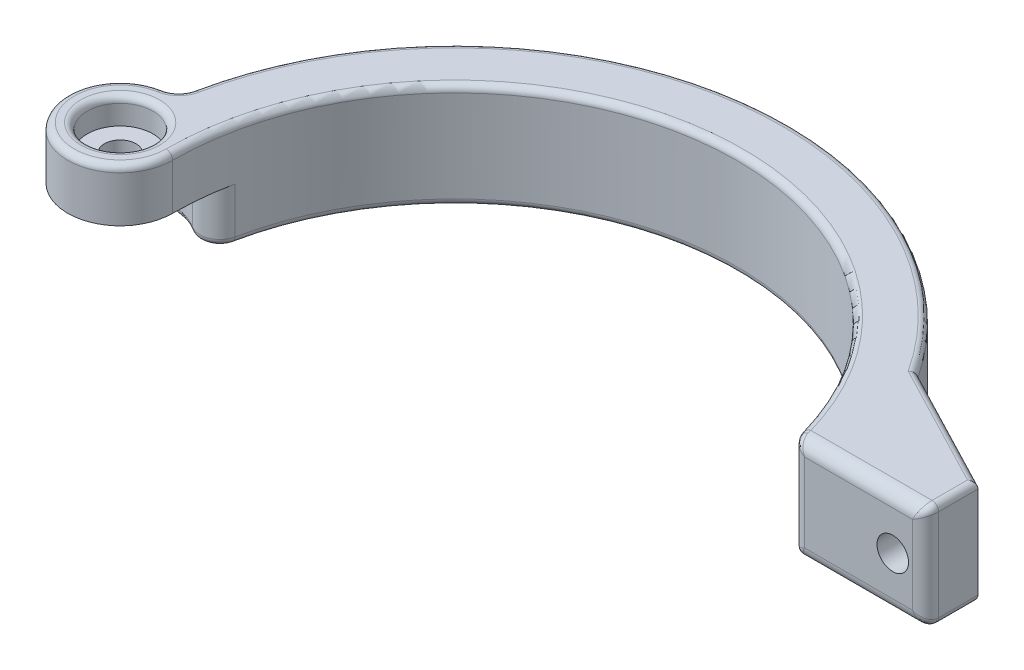
SolidWorks part; units mm, degrees
material "PET"
ref_plane "Front Plane" through (0, 0, 0) normal (0, 0, 1) x (1, 0, 0)
ref_plane "Top Plane" through (0, 0, 0) normal (0, 1, 0) x (1, 0, 0)
ref_plane "Right Plane" through (0, 0, 0) normal (1, 0, 0) x (0, 0, -1)
sketch "Sketch1" plane through (0, 0, 0) normal (0, 0, 1) x (1, 0, 0)
  line L0 (0, 0) -> (0, 16) construction
  line L1 (43, 0) -> (43, 16)
  line L2 (43, 16) -> (51, 16)
  line L3 (51, 16) -> (51, 0)
  line L4 (51, 0) -> (43, 0)
  dimension "D1" = 86
  dimension "D2" = 16
  dimension "D3" = 8
revolve "body" add sketch "Sketch1" angle 180 about L0
sketch "Sketch2" plane through (0, 16, 0) normal (0, 1, 0) x (1, 0, 0)
  circle A0 centre (-51, 0) radius 8
extrude "bearing_body" add sketch "Sketch2" against normal blind 8
sketch "Sketch3" plane through (0, 8, 0) normal (0, -1, 0) x (1, 0, 0)
  circle A0 centre (-51, 0) radius 8
  arc A1 (-43, 0) -> (-50.3725, -7.9754) centre (-51, 0) ccw construction
extrude "bearing_cutout" cut sketch "Sketch3" along normal through all
fillet "bearing_fillets" radius 3 2 edges at (-50.3725, 12, -7.9754) (-43, 4, 0)
sketch "Sketch4" plane through (0, 0, 0) normal (0, -1, 0) x (1, 0, 0)
  line L1 (51, 0) -> (41.821, 0)
  line L2 (51, 0) -> (51, -10)
  line L3 (51, -10) -> (41.821, -10)
  line L4 (41.821, 0) -> (41.821, -10)
  arc A0 (-50.3725, -7.9754) -> (51, 0) centre (0, 0) ccw construction
  arc A1 (-42.1202, -8.6538) -> (43, 0) centre (0, 0) ccw construction
  dimension "D1" = 10
extrude "tightening_cutout" cut sketch "Sketch4" against normal through all
sketch "Sketch5" plane through (0, 0, 0) normal (0, -1, 0) x (1, 0, 0)
  line L0 (41.821, -10) -> (61.821, -10)
  line L2 (42.6263, -28) -> (41.821, -10)
  line L3 (61.821, -10) -> (61.821, -18)
  line L4 (61.821, -18) -> (42.6263, -28)
  arc A0 (-50.3725, -7.9754) -> (50.01, -10) centre (0, 0) ccw construction
  dimension "D1" = 20
  dimension "D2" = 8
  dimension "D3" = 10
extrude "tightening_body" add sketch "Sketch5" against normal up to vertex (16 mm away) up to point (50.01, 16, -10)
ref_plane "tightening_screw_hole_plane" through (0, 0, -28) normal (0, 0, 1) x (1, 0, 0)
sketch "Sketch6" plane through (0, 0, -28) normal (0, 0, 1) x (1, 0, 0)
  line L0 (41.821, 0) -> (61.821, 0) construction
  line L1 (61.821, 16) -> (61.821, 0) construction
  point P0 (56.821, 8)
  dimension "D1" = 8
  dimension "D2" = 5
hole_wizard "tightening_screw_hole" positions "Sketch6" profile "Sketch7" counterbore size "M4" standard "DIN" end condition through all
sketch "Sketch7" plane through (56.821, 8, -28) normal (1, 0, 0) x (0, 1, 0)
  line L0 (0, 0) -> (0, 36)
  line L1 (0, 36) -> (2.4, 36)
  line L3 (2.4, 36) -> (2.4, 9)
  line L4 (2.4, 9) -> (5, 9)
  line L5 (5, 9) -> (5, 0)
  line L7 (5, 0) -> (0, 0)
  line L11 (0, -6.35) -> (0, 107.95) construction
  dimension "Thru Hole Dia." = 4.8
  dimension "Thru Hole Depth" = 36
  dimension "C'Bore Dia." = 10
  dimension "C'Bore Depth" = 9
sketch "Sketch8" plane through (0, 16, 0) normal (0, 1, 0) x (1, 0, 0)
  point P0 (-51, 0)
hole_wizard "bearing_screw_hole" positions "Sketch8" profile "Sketch9" counterbore size "M4" standard "DIN" end condition through all
sketch "Sketch9" plane through (-51, 16, 0) normal (1, 0, 0) x (0, 0, 1)
  line L0 (0, 0) -> (0, 16)
  line L1 (0, 16) -> (2.4, 16)
  line L3 (2.4, 16) -> (2.4, 4)
  line L4 (2.4, 4) -> (5, 4)
  line L5 (5, 4) -> (5, 0)
  line L7 (5, 0) -> (0, 0)
  line L11 (0, -6.35) -> (0, 107.95) construction
  dimension "Thru Hole Dia." = 4.8
  dimension "Thru Hole Depth" = 16
  dimension "C'Bore Dia." = 10
  dimension "C'Bore Depth" = 4
fillet "tightening_block_fillets" radius 2 4 edges at (41.821, 8, -10) (51.821, 0, -10) (61.821, 8, -10) (51.821, 16, -10)
fillet "general_fillets" radius 1 19 edges at (61.2353, 15.4142, -10.5858) (42.1594, 15.2111, -10.4084) (42.1594, 0.7889, -10.4084) (61.2353, 0.5858, -10.5858) (-56.1446, 16, 6.1264) (-50.8108, 16, -8.6833) (-9.6114, 16, -50.0861) (52.2237, 16, -23) (61.821, 16, -15) (-6.0605, 16, -42.5708) (-51, 16, 5) (52.2237, 0, -23) (-10.7354, 0, -49.8573) (-48.449, 0, -7.5824) (-43.8939, 0, -6.493) (-1.7236, 0, -42.9654) (61.821, 0, -15)
equation "\"paper_size\" = 600mm"
equation "\"cb_roll_d_outer\" = 86mm"
equation "\"cb_roll_d_inner\" = 76mm"
equation "\"helper_d\" = 92mm"
equation "\"outer_d\" = 112mm"
equation "\"spring_l_max\" = 25mm"
equation "\"spring_l_min\" = 10mm"
equation "\"attached_len\" = \"spring_l_max\" * 2 - \"spring_l_min\" + 18"
equation "\"cone_d_larger\" = 40mm"
equation "\"cone_angle\" = 60deg"
equation "\"bottom_screw_ring_d\" = 92mm"
equation "\"D1@Sketch1\"=\"cb_roll_d_outer\""
